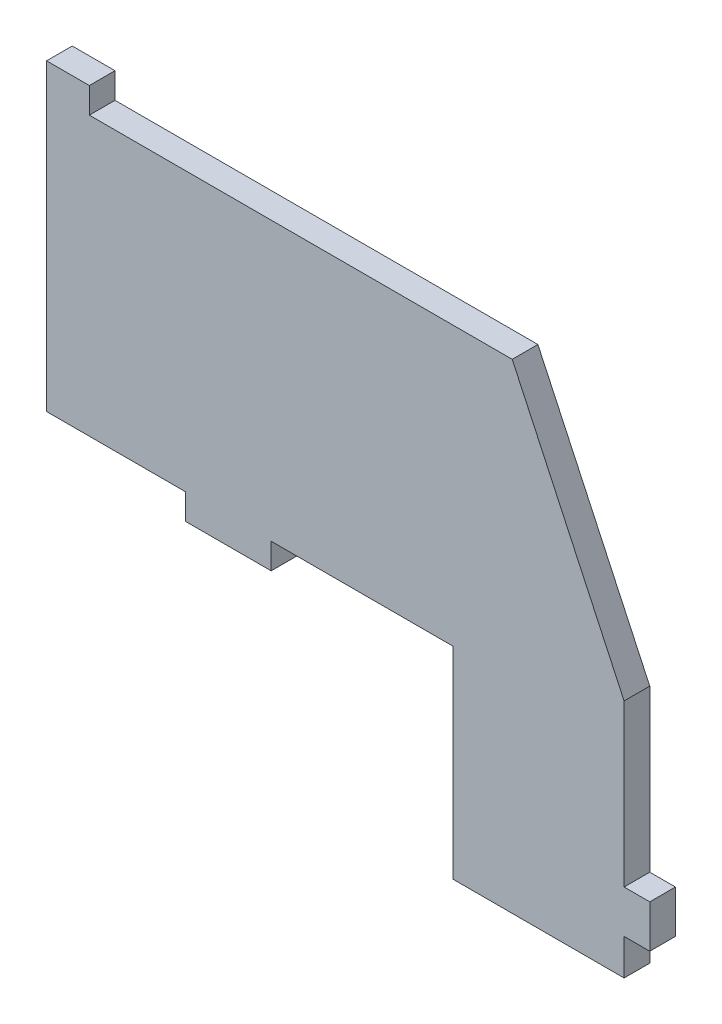
SolidWorks part; units mm, degrees
ref_plane "Plan de face" through (0, 0, 0) normal (0, 0, 1) x (1, 0, 0)
ref_plane "Plan de dessus" through (0, 0, 0) normal (0, 1, 0) x (1, 0, 0)
ref_plane "Plan de droite" through (0, 0, 0) normal (1, 0, 0) x (0, 0, -1)
sketch "Esquisse1" plane through (0, 0, 0) normal (0, 0, 1) x (1, 0, 0)
  line L1 (-67.5, 56.085) -> (67.5, 56.085)
  line L2 (-67.5, 56.085) -> (-67.5, -56.085)
  line L3 (-67.5, -56.085) -> (67.5, -56.085)
  line L4 (67.5, 56.085) -> (67.5, -56.085)
  point P7 (5.8405, 59.6459)
  dimension "D1" = 135
  dimension "D2" = 112.17
  dimension "D3" = 67.5
  dimension "D4" = 56.085
extrude "Boss.-Extru.1" add sketch "Esquisse1" along normal blind 6
sketch "Esquisse2" plane through (0, 0, 6) normal (0, 0, 1) x (1, 0, 0)
  line L0 (-67.5, -56.085) -> (67.5, -56.085) construction
  line L1 (27.5, -56.085) -> (-67.5, -56.085)
  line L2 (27.5, -56.085) -> (27.5, -8.915)
  line L3 (27.5, -8.915) -> (-67.5, -8.915)
  line L4 (-67.5, -56.085) -> (-67.5, -8.915)
  line L5 (-67.5, 56.085) -> (-67.5, -56.085) construction
  line L6 (67.5, -56.085) -> (67.5, 56.085) construction
  line L7 (67.5, 0) -> (41.3471, 56.085)
  line L8 (67.5, 56.085) -> (-67.5, 56.085) construction
  line L9 (41.3471, 56.085) -> (67.5, 56.085)
  line L10 (67.5, 56.085) -> (67.5, 0)
  dimension "D1" = 47.17
  dimension "D2" = 95
  dimension "D3" = 155
  dimension "D4" = 115
extrude "Enlèv. mat.-Extru.1" cut sketch "Esquisse2" against normal blind 6
sketch "Esquisse3" plane through (0, 0, 6) normal (0, 0, 1) x (1, 0, 0)
  line L0 (67.5, -56.085) -> (67.5, 0) construction
  line L1 (67.5, -47.665) -> (73.5, -47.665)
  line L2 (67.5, -47.665) -> (67.5, -37.665)
  line L3 (67.5, -37.665) -> (73.5, -37.665)
  line L4 (73.5, -47.665) -> (73.5, -37.665)
  line L5 (27.5, -8.915) -> (-67.5, -8.915) construction
  line L6 (-35, -8.915) -> (-15, -8.915)
  line L7 (-35, -8.915) -> (-35, -14.915)
  line L8 (-35, -14.915) -> (-15, -14.915)
  line L9 (-15, -8.915) -> (-15, -14.915)
  line L10 (41.3471, 56.085) -> (-67.5, 56.085) construction
  line L11 (-67.5, 56.085) -> (-57.5, 56.085)
  line L12 (-67.5, 56.085) -> (-67.5, 62.085)
  line L13 (-67.5, 62.085) -> (-57.5, 62.085)
  line L14 (-57.5, 56.085) -> (-57.5, 62.085)
  line L16 (27.5, -56.085) -> (27.5, -8.915) construction
  line L17 (27.5, -56.085) -> (67.5, -56.085) construction
  dimension "D1" = 6
  dimension "D2" = 10
  dimension "D3" = 6
  dimension "D4" = 20
  dimension "D5" = 42.5
  dimension "D6" = 10
  dimension "D7" = 6
  dimension "D8" = 8.42
extrude "Boss.-Extru.2" add sketch "Esquisse3" against normal blind 6
equation "\"D3@Esquisse1\"=\"D1@Esquisse1\"/2"
equation "\"D4@Esquisse1\"=\"D2@Esquisse1\"/2"
